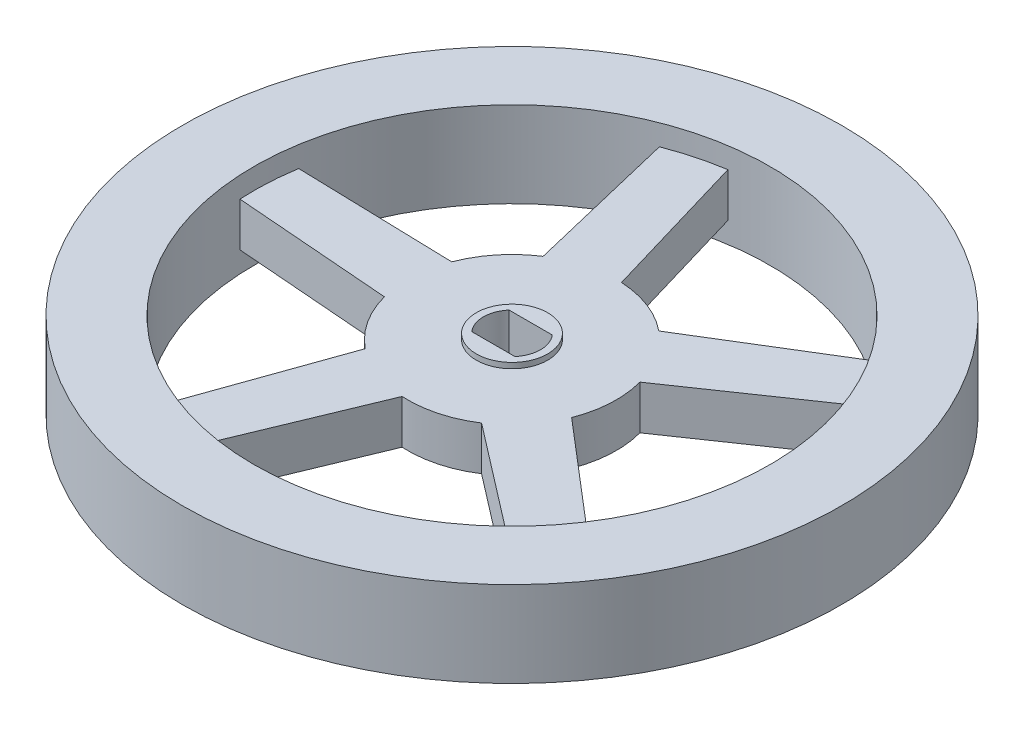
SolidWorks part; units mm, degrees
ref_plane "Front Plane" through (0, 0, 0) normal (0, 0, 1) x (1, 0, 0)
ref_plane "Top Plane" through (0, 0, 0) normal (0, 1, 0) x (1, 0, 0)
ref_plane "Right Plane" through (0, 0, 0) normal (1, 0, 0) x (0, 0, -1)
sketch "Sketch1" plane through (0, 0, 0) normal (0, 1, 0) x (1, 0, 0)
  line L0 (-2.4531, 9.1778) -> (-6.0683, 22.703)
  line L1 (-1.9672, 1.7) -> (1.9672, 1.7)
  line L2 (-1.9672, 1.7) -> (-1.9672, -1.7)
  line L3 (-1.9672, -1.7) -> (1.9672, -1.7)
  line L4 (1.9672, 1.7) -> (1.9672, -1.7)
  line L5 (-5.1503, 7.9828) -> (-8.4925, 21.9118)
  line L6 (0.4805, 9.4878) -> (-3.5727, 23.2268)
  line L7 (6.0006, 7.365) -> (18.2151, 14.8479)
  line L8 (9.172, 2.4749) -> (20.986, 10.5753)
  line L9 (8.8588, -3.431) -> (19.75, -12.7353)
  line L10 (5.1881, -7.9583) -> (16.5428, -16.6909)
  line L11 (-0.5255, -9.4855) -> (-6.0089, -22.7188)
  line L12 (-5.9656, -7.3934) -> (-10.762, -20.8909)
  line L13 (-9.1836, -2.4314) -> (-23.4637, -1.3057)
  line L14 (-8.875, 3.3889) -> (-23.1941, 3.7797)
  circle A0 centre (0, 0) radius 30
  circle A1 centre (0, 0) radius 3.25
  circle A2 centre (0, 0) radius 2.6
  circle A3 centre (0, 0) radius 9.5
  circle A4 centre (0, 0) radius 23.5
  circle A5 centre (0, 0) radius 1
  point P36 (0, 0)
  dimension "D1" = 60
  dimension "D2" = 6.5
  dimension "D3" = 5.2
  dimension "D4" = 19
  dimension "D5" = 47
  dimension "D10" = 2
  dimension "D6" = 3.4
  dimension "D7" = 2.95
  dimension "D8" = 2.55
  dimension "D9" = 5
extrude "Boss-Extrude1" add sketch "Sketch1" along normal blind 4 contours L14 A4 L13 A3 | A3 A1 | L12 A4 L11 A3 | L10 A4 L9 A3 | L8 A4 L7 A3 | L6 A4 L0 A3 | L0 A4 L5 A3 region at (-5.5193, 0, -15.3397) region at (-2.8703, 0, -16.0477) region at (-0.9702, 0, -9.1802) region at (13.6293, 0, -8.8391) region at (-16.2218, 0, -0.8601) region at (-5.8309, 0, 15.1621) region at (12.6182, 0, 10.2308)
extrude "Boss-Extrude2" add sketch "Sketch1<4>" along normal blind 4.5 contours L1 A2 | A1 A2 | L3 A2 region at (0, 0, -2.0659) region at (0, 0, 2.0659) region at (-3.1581, 0, 0)
sketch "Sketch1<4>" plane through (0, 0, 0) normal (0, 1, 0) x (1, 0, 0) same geometry as "Sketch1"
extrude "Boss-Extrude3" add sketch "Sketch1<5>" along normal blind 0.5 contours L4 A2 | L4 L1 L2 L3 A5 | L2 A2 region at (0, 0, -1.648) region at (-2.2232, 0, 0) region at (2.2232, 0, 0)
sketch "Sketch1<5>" plane through (0, 0, 0) normal (0, 1, 0) x (1, 0, 0) same geometry as "Sketch1"
extrude "Boss-Extrude4" add sketch "Sketch1<6>" along normal blind 5.9 and the other way blind 1.9 contours A0 A4 region at (-29.1515, 0, 0)
sketch "Sketch1<6>" plane through (0, 0, 0) normal (0, 1, 0) x (1, 0, 0) same geometry as "Sketch1"
